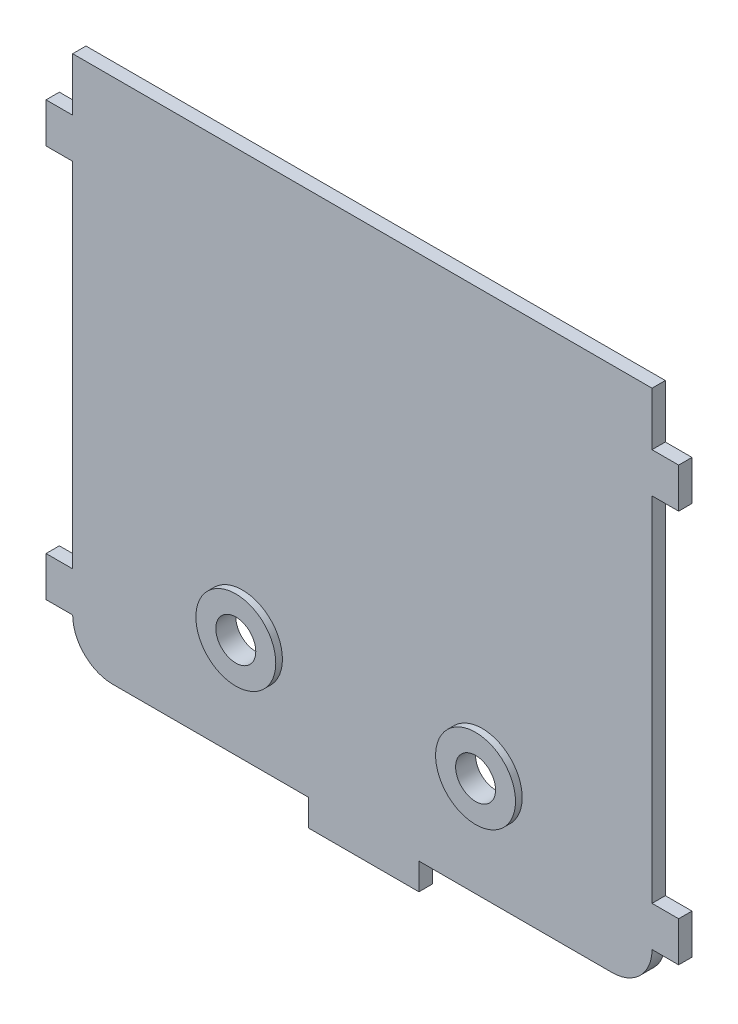
SolidWorks part; units mm, degrees
ref_plane "Front Plane" through (0, 0, 0) normal (0, 0, 1) x (1, 0, 0)
ref_plane "Top Plane" through (0, 0, 0) normal (0, 1, 0) x (1, 0, 0)
ref_plane "Right Plane" through (0, 0, 0) normal (1, 0, 0) x (0, 0, -1)
sketch "Sketch1" plane through (0, 0, 0) normal (0, 0, 1) x (1, 0, 0)
  line L1 (21.75, -19.75) -> (-21.75, -19.75)
  line L2 (21.75, -19.75) -> (21.75, 19.75)
  line L3 (21.75, 19.75) -> (-21.75, 19.75)
  line L4 (-21.75, -19.75) -> (-21.75, 19.75)
  line L5 (21.75, -19.75) -> (-21.75, 19.75) construction
  line L6 (21.75, 19.75) -> (-21.75, -19.75) construction
  point P0 (0, 0)
  dimension "D1" = 43.5
  dimension "D2" = 39.5
extrude "body" add sketch "Sketch1" along normal blind 1
sketch "Sketch2" plane through (21.75, 0, 0) normal (1, 0, 0) x (0, 0, -1)
  line L0 (-1, -19.75) -> (-1, 19.75) construction
  line L1 (-1, 15.75) -> (0, 15.75)
  line L2 (-1, 15.75) -> (-1, 12.75)
  line L3 (-1, 12.75) -> (0, 12.75)
  line L4 (0, 15.75) -> (0, 12.75)
  line L5 (0, -19.75) -> (0, 19.75) construction
  line L6 (-1, -19.75) -> (0, -19.75) construction
  line L7 (-1, -13.75) -> (0, -13.75)
  line L8 (-1, -13.75) -> (-1, -16.75)
  line L9 (-1, -16.75) -> (0, -16.75)
  line L10 (0, -13.75) -> (0, -16.75)
  line L11 (-1, 19.75) -> (0, 19.75) construction
  point P14 (-0.5, -16.75)
  point P17 (-0.5, 19.75)
  dimension "D1" = 26.5
  dimension "D2" = 3
  dimension "D3" = 3
  dimension "D4" = 3
  dimension "D5" = 4
extrude "clips_r" add sketch "Sketch2" along normal blind 2
sketch "Sketch3" plane through (-21.75, 0, 0) normal (-1, 0, 0) x (0, 0, 1)
  line L0 (1, 19.75) -> (0, 19.75) construction
  line L12 (0, 19.75) -> (0, -19.75) construction
  line L13 (0, -13.75) -> (1, -13.75)
  line L14 (0, -13.75) -> (0, -16.75)
  line L15 (0, -16.75) -> (1, -16.75)
  line L16 (1, -13.75) -> (1, -16.75)
  line L17 (1, 19.75) -> (1, -19.75) construction
  line L18 (1, -19.75) -> (0, -19.75) construction
  line L19 (0, 15.75) -> (1, 15.75)
  line L20 (0, 15.75) -> (0, 12.75)
  line L21 (0, 12.75) -> (1, 12.75)
  line L22 (1, 15.75) -> (1, 12.75)
  point P4 (0.5, 15.75)
  dimension "D1" = 3
  dimension "D2" = 3
  dimension "D3" = 26.5
  dimension "D4" = 3
  dimension "D5" = 4
extrude "clips_l" add sketch "Sketch3" along normal blind 2
sketch "Sketch4" plane through (0, -19.75, 0) normal (0, -1, 0) x (1, 0, 0)
  line L0 (-21.75, 1) -> (21.75, 1) construction
  line L1 (-4.0496, 1) -> (4.25, 1)
  line L2 (-4.0496, 1) -> (-4.0496, 0)
  line L3 (-4.0496, 0) -> (4.25, 0)
  line L4 (4.25, 1) -> (4.25, 0)
  line L5 (-21.75, 0) -> (21.75, 0) construction
  line L6 (21.75, 1) -> (21.75, 0) construction
  dimension "D1" = 8.2996
  dimension "D2" = 17.5
extrude "clips_b" add sketch "Sketch4" along normal blind 2
sketch "Sketch5" plane through (0, 0, 1) normal (0, 0, 1) x (1, 0, 0)
  line L0 (-21.75, -11.75) -> (21.75, -11.75) construction
  line L1 (-21.75, 12.75) -> (-21.75, -13.75) construction
  line L2 (21.75, -13.75) -> (21.75, 12.75) construction
  line L3 (-21.75, -19.75) -> (-4.0496, -19.75) construction
  line L4 (0.1002, -21.75) -> (0, -11.75) construction
  line L5 (4.25, -21.75) -> (-4.0496, -21.75) construction
  circle A1 centre (9.0005, -11.75) radius 3
  circle A2 centre (-9.0005, -11.75) radius 3
  dimension "D4" = 6
  dimension "D5" = 6
  dimension "D1" = 8
  dimension "D2" = 9
  dimension "D3" = 9
extrude "paddle_support" add sketch "Sketch5" along normal blind 0.5
sketch "Sketch6" plane through (0, 0, 1.5) normal (0, 0, 1) x (1, 0, 0)
  circle A0 centre (-9.0005, -11.75) radius 1.5
  circle A2 centre (9.0005, -11.75) radius 1.5
  dimension "D1" = 3
  dimension "D2" = 3
extrude "bolts" cut sketch "Sketch6" against normal through all
fillet "Fillet1" radius 3 2 edges at (-21.75, -19.75, 0.5) (21.75, -19.75, 0.5)
